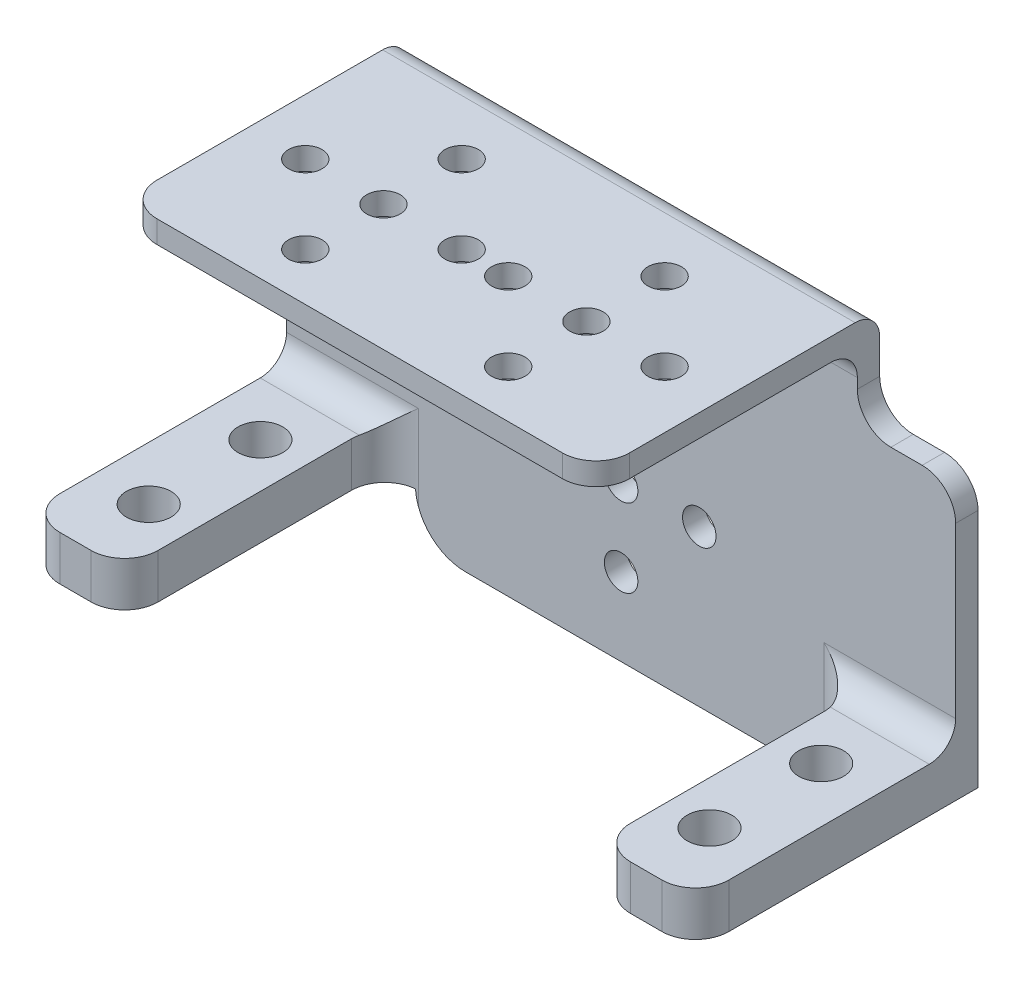
SolidWorks part; units mm, degrees
ref_plane "前视基准面" through (0, 0, 0) normal (0, 0, 1) x (1, 0, 0)
ref_plane "上视基准面" through (0, 0, 0) normal (0, 1, 0) x (1, 0, 0)
ref_plane "右视基准面" through (0, 0, 0) normal (1, 0, 0) x (0, 0, -1)
sketch "Sketch1" plane through (0, 0, 0) normal (0, 0, 1) x (1, 0, 0)
  line L0 (-21.15, 16.48) -> (21.15, 16.48)
  line L1 (-21.15, 18.48) -> (21.15, 18.48)
  line L2 (-21.15, 18.48) -> (-21.15, -14.28)
  line L3 (-4.3498, -18.48) -> (13.96, -18.48)
  line L4 (21.15, 18.48) -> (21.15, -14.28)
  line L5 (-13.96, -18.48) -> (-4.3498, -18.48)
  line L6 (-18.4, -9.12) -> (18.4, -9.12)
  line L7 (-18.4, -9.12) -> (-18.4, -14.04)
  line L8 (-13.96, -18.48) -> (13.96, -18.48)
  line L9 (18.4, -9.12) -> (18.4, -14.04)
  line L10 (-4.3498, -18.48) -> (13.96, -18.48)
  line L11 (-21.15, -14.28) -> (-18.3935, -14.28)
  line L12 (21.15, 10.22) -> (29.95, 10.22)
  line L13 (21.15, 10.22) -> (21.15, -14.28)
  line L14 (21.15, -14.28) -> (29.95, -14.28)
  line L15 (29.95, 10.22) -> (29.95, -14.28)
  line L16 (-29.95, 10.22) -> (-21.15, 10.22)
  line L17 (-29.95, 10.22) -> (-29.95, -14.28)
  line L18 (-29.95, -14.28) -> (-21.15, -14.28)
  line L19 (-21.15, 10.22) -> (-21.15, -14.28)
  line L23 (21.15, -14.28) -> (18.3935, -14.28)
  line L24 (21.15, -10.28) -> (29.95, -10.28)
  line L25 (21.15, -10.28) -> (21.15, -14.28)
  line L26 (21.15, -14.28) -> (29.95, -14.28)
  line L27 (29.95, -10.28) -> (29.95, -14.28)
  line L28 (-29.95, -10.28) -> (-21.15, -10.28)
  line L29 (-29.95, -10.28) -> (-29.95, -14.28)
  line L30 (-29.95, -14.28) -> (-21.15, -14.28)
  line L31 (-21.15, -10.28) -> (-21.15, -14.28)
  arc A0 (-13.96, -18.48) -> (-18.4, -14.04) centre (-13.96, -14.04) cw
  arc A1 (13.96, -18.48) -> (18.4, -14.04) centre (13.96, -14.04) ccw
  point P20 (18.4, -18.48)
  point P30 (-25.55, -14.28)
  point P32 (-25.55, -10.28)
  dimension "D9" = 4.44
  dimension "D10" = 4.44
  dimension "D2" = 42.3
  dimension "D3" = 21.15
  dimension "D4" = 18.48
  dimension "D5" = 2
  dimension "D6" = 9.36
  dimension "D7" = 36.8
  dimension "D8" = 18.4
  dimension "D11" = 18.48
  dimension "D12" = 24.5
  dimension "D13" = 24.5
  dimension "D14" = 8.8
  dimension "D15" = 8.8
  dimension "D17" = 32.76
  dimension "D18" = 4
  dimension "D19" = 4
extrude "Boss-Extrude1" add sketch "Sketch1" along normal blind 2 contours L6 L4 L0 L2 | L3 A1 L9 L6 L7 A0 L5 | L17 L28 L19 L2 L16 | L4 L24 L15 L12 region at (0, 3.2872, 0) region at (-25.55, -0.03, 0) region at (25.55, -0.03, 0) region at (0, -13.7071, 0)
extrude "Boss-Extrude2" add sketch "Sketch1<3>" along normal blind 25.4 contours L4 L1 L2 L0 region at (0, 17.48, 0)
sketch "Sketch1<3>" plane through (0, 0, 0) normal (0, 0, 1) x (1, 0, 0) same geometry as "Sketch1"
extrude "Boss-Extrude3" add sketch "Sketch1<4>" along normal blind 25.3 contours L28 L17 L18 L2 | L24 L13 L14 L15 region at (-25.55, -12.28, 0) region at (25.55, -12.28, 0)
sketch "Sketch1<4>" plane through (0, 0, 0) normal (0, 0, 1) x (1, 0, 0) same geometry as "Sketch1"
fillet "Fillet31" radius 3 12 edges at (21.15, -12.28, 25.3) (29.95, -12.28, 25.3) (21.15, 17.48, 25.4) (-21.15, 17.48, 25.4) (-29.95, -12.28, 25.3) (-21.15, -12.28, 25.3) (-29.95, 10.22, 1) (-21.15, 10.22, 1) (21.15, 10.22, 1) (29.95, 10.22, 1) (21.15, -12.28, 2) (-21.15, -12.28, 2)
fillet "Fillet32" radius 2.36 3 edges at (24.05, -10.28, 2) (-24.05, -10.28, 2) (0, 16.48, 2)
sketch "Sketch2" plane through (0, -14.28, 0) normal (0, -1, 0) x (1, 0, 0)
  line L0 (24.15, 25.3) -> (26.95, 25.3) construction
  line L1 (25.05, 19.14) -> (25.05, 9.14) construction
  line L2 (21.15, 22.3) -> (21.15, 5) construction
  line L3 (-26.95, 25.3) -> (-24.15, 25.3) construction
  line L5 (-21.15, 22.3) -> (-21.15, 5) construction
  circle A0 centre (25.05, 19.14) radius 2
  circle A1 centre (25.05, 9.14) radius 2
  circle A2 centre (-25.15, 19.14) radius 2
  circle A3 centre (-25.15, 9.14) radius 2
  dimension "D1" = 4
  dimension "D2" = 4
  dimension "D7" = 4
  dimension "D8" = 4
  dimension "D3" = 6.16
  dimension "D4" = 10
  dimension "D5" = 3.9
  dimension "D9" = 6.16
  dimension "D10" = 4
  dimension "D11" = 10
fillet "Fillet26" radius 2.2 1 edges at (0, 18.48, 0) type face fillet first side face at (0, 1.4296, 0) second side face at (0, 18.48, 16.1404)
fillet "Fillet28" [suppressed] radius 0.5
fillet "Fillet29" [suppressed] radius 0.5
fillet "Fillet30" [suppressed] radius 1
extrude "Cut-Extrude1" cut sketch "Sketch2" against normal mid plane 20
sketch "Sketch3" plane through (0, 18.48, 0) normal (0, 1, 0) x (1, 0, 0)
  line L0 (21.15, -2.2) -> (-21.15, -2.2) construction
  line L1 (-21.15, -22.4) -> (-21.15, -2.2) construction
  line L2 (-18.15, -25.4) -> (18.15, -25.4) construction
  line L3 (21.15, -22.4) -> (21.15, -2.2) construction
  line L4 (0, -34.8199) -> (0, 24.3344) construction
  circle A5 centre (-9.1346, -14.14) radius 1.5
  circle A6 centre (-9.1346, -7.14) radius 1.5
  circle A7 centre (-2.1346, -14.14) radius 1.5
  circle A8 centre (-9.1346, -21.14) radius 1.5
  circle A9 centre (-16.1346, -14.14) radius 1.5
  circle A10 centre (9.0346, -14.14) radius 1.5
  circle A11 centre (9.0346, -7.14) radius 1.5
  circle A12 centre (16.0346, -14.14) radius 1.5
  circle A13 centre (9.0346, -21.14) radius 1.5
  circle A14 centre (2.0346, -14.14) radius 1.5
  point P31 (-9.1346, -14.14)
  point P34 (9.0346, -14.14)
  point P43 (9.0346, -14.14)
  dimension "D2" = 7
  dimension "D7" = 3
  dimension "D8" = 3
  dimension "D3" = 3
  dimension "D4" = 3
  dimension "D5" = 4
  dimension "D6" = 12.0154
  dimension "D10" = 4.94
  dimension "D11" = 23.2
  dimension "D12" = 42.3
  dimension "D9" = 4
extrude "Cut-Extrude2" cut sketch "Sketch3" against normal blind 10
sketch "Sketch4" plane through (0, 0, 0) normal (0, 0, -1) x (-1, 0, 0)
  line L3 (18.4, -9.12) -> (21.15, -9.12)
  line L4 (-21.15, 18.48) -> (21.15, 18.48) construction
  line L5 (-21.15, 18.48) -> (21.15, 18.48)
  circle A0 centre (0, 2.48) radius 1.5
  circle A1 centre (0, -4.52) radius 1.5
  circle A2 centre (0, -11.52) radius 1.5
  circle A3 centre (7, -4.52) radius 1.5
  circle A4 centre (-7, -4.52) radius 1.5
  dimension "D1" = 3
  dimension "D2" = 3
  dimension "D4" = 3
  dimension "D6" = 3
  dimension "D8" = 3
  dimension "D3" = 7
  dimension "D5" = 7
  dimension "D7" = 7
  dimension "D9" = 7
  dimension "D10" = 23
extrude "Cut-Extrude3" cut sketch "Sketch4" against normal blind 10 contours A4 | A0 | A3 | A2 | A1 region at (0, 2.48, 0) region at (0, -11.52, 0) region at (-7, -4.52, 0) region at (7, -4.52, 0)
